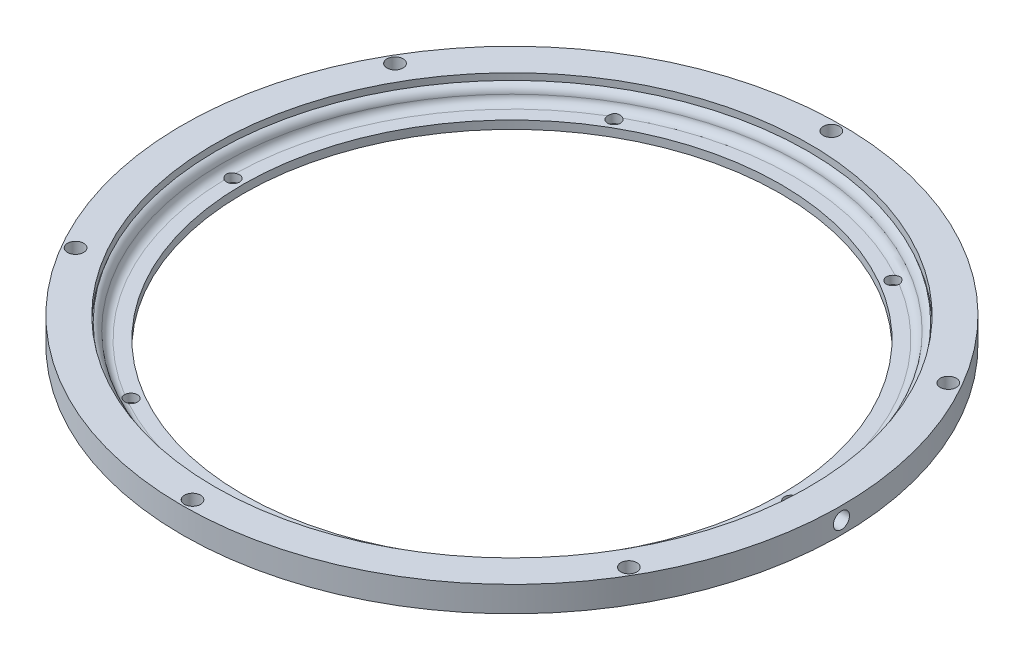
SolidWorks part; units mm, degrees
note: '?' marks a value the reader was unsure of.
ref_plane "Front" through (0, 0, 0) normal (0, 0, 1) x (1, 0, 0)
ref_plane "Top" through (0, 0, 0) normal (0, 1, 0) x (1, 0, 0)
ref_plane "Right" through (0, 0, 0) normal (1, 0, 0) x (0, 0, -1)
ref_axis "Axis1" through (0, 15.0019, 0) along (0, -1, 0)?
sketch "Sketch1" plane through (0, 0, 0) normal (0, 0, 1) x (1, 0, 0)
  line L0 (0, 8.551) -> (0, -4.9357) construction
  line L1 (162.5, 14.2875) -> (162.5, 1.7335)
  line L2 (162.5, 14.2875) -> (146.5, 14.2875)
  line L3 (146.5, 14.2875) -> (146.5, 10.0753)
  line L4 (149.5, 1.7335) -> (162.5, 1.7335)
  line L5 (132.516, 0) -> (148, 0)
  line L6 (132.516, 0) -> (162.5, 14.2875) construction
  line L7 (149.5, 1.7335) -> (149.5, 4.7685)
  line L9 (132.516, 4) -> (132.516, 0)
  line L10 (146.5, 10.0753) -> (149.5, 4.7685) construction
  line L11 (148, 0) -> (148, 4.083)
  line L12 (146, 11.3836) -> (146, 9.8522)
  line L13 (139.0875, 4) -> (132.516, 4)
  arc A0 (146, 9.8522) -> (148, 4.083) centre (147.508, 7.1438) ccw
  arc A1 (146, 11.3836) -> (143.029, 7.5779) centre (147.508, 7.1438) ccw
  arc A2 (139.0875, 4) -> (143.029, 7.5779) centre (139.0875, 7.96) ccw
  arc A3 (149.5, 4.7685) -> (146.5, 10.0753) centre (147.508, 7.1438) ccw
  point P17 (148, 7.4219)
  dimension "D8" = 6.2
  dimension "D9" = 9
  dimension "D2" = 14.2875
  dimension "D3" = 29.984
  dimension "D4" = 16
  dimension "D5" = 12.554
  dimension "D6" = 13
  dimension "D7" = 4
  dimension "D10" = 0.5
  dimension "D11" = 325
  dimension "D12" = 278.175
  dimension "D13" = 1.7335
  dimension "D14" = 265.032
revolve "Revolve2" add sketch "Sketch1" angle 360 about L0
sketch "Sketch2" plane through (0, 0, 0) normal (0, -1, 0) x (1, 0, 0)
  line L0 (0, 0) -> (167.0886, 0) construction
  line L1 (0, 0) -> (86.0025, -148.9607) construction
  line L2 (132.516, 4.1036) -> (132.516, -4.7686) construction
  line L3 (134.516, 3.5121) -> (134.516, -5.9515) construction
  line L4 (137.5, 0) -> (140.484, 0) construction
  line L5 (134.516, 0) -> (137.5, 0) construction
  line L6 (139.657, -6.35) -> (135.2215, -6.35) construction
  line L7 (73.5238, -114.647) -> (75.5358, -118.1318) construction
  arc A0 (75.0109, -111.6598) -> (134.2057, -9.1314) centre (0, 0) ccw
  arc A1 (78.3389, -116.6138) -> (140.1599, -9.5366) centre (0, 0) ccw
  circle A2 centre (0, 0) radius 137.5 construction
  circle A3 centre (0, 0) radius 132.516 construction
  arc A4 (140.1599, -9.5366) -> (134.2057, -9.1314) centre (137.1828, -9.334) ccw
  arc A5 (75.0109, -111.6598) -> (78.3389, -116.6138) centre (76.6749, -114.1368) ccw
  dimension "D2" = 275
  dimension "D1" = 60
  dimension "D3" = 2
  dimension "D4" = 6.35
  dimension "D5" = 6.35
extrude "Cut-Extrude1" cut sketch "Sketch2" against normal offset from surface (0.3165 mm away) 3.81
pattern_circular "CirPattern1" count 6 over 360 about axis through (0, 0, 0) along (0, 1, 0) of "Cut-Extrude1"
sketch "Sketch3" plane through (0, 1.7335, 0) normal (0, -1, 0) x (1, 0, 0)
  line L0 (0, 0) -> (149.5, 86.3139) construction
  line L1 (0, 0) -> (154.2972, -89.0835) construction
  line L2 (0, 0) -> (63.0511, 0) construction
  line L3 (142.7957, 73.2777) -> (134.9914, 68.7719)
  line L4 (134.9914, -68.7719) -> (142.7957, -73.2777)
  line L5 (162.5, 4.9183) -> (162.5, -33.5059) construction
  line L6 (160.5, 8.5668) -> (160.5, -35.0892) construction
  line L7 (151.5, 7.4564) -> (151.5, -22.8744) construction
  line L8 (149.5, -1.1233) -> (149.5, -18.1031) construction
  arc A0 (142.7957, -73.2777) -> (142.7957, 73.2777) centre (0, 0) ccw
  arc A1 (134.9914, -68.7719) -> (134.9914, 68.7719) centre (0, 0) ccw
  circle A2 centre (0, 0) radius 149.5 construction
  circle A3 centre (0, 0) radius 162.5 construction
  dimension "D1" = 60
  dimension "D2" = 30
  dimension "D3" = 7.9375
  dimension "D4" = 7.9375
  dimension "D5" = 2
  dimension "D6" = 2
extrude "Cut-Extrude2" cut sketch "Sketch3" against normal blind 10
pattern_circular "CirPattern2" count 6 over 360 about axis through (0, 0, 0) along (0, 1, 0) of "Cut-Extrude2"
sketch "Sketch5" plane through (0, 4, 0) normal (0, 1, 0) x (-1, 0, 0)
  line L0 (0, 0) -> (-68.75, -119.0785) construction
  line L1 (17.7406, -10.2426) -> (-18.7249, 10.8108) construction
  line L2 (0, 0) -> (0, -87.4239) construction
  circle A0 centre (-68.75, -119.0785) radius 3.175
  dimension "D1" = 6.35
  dimension "D2" = 275
  dimension "D3" = 30
extrude "Cut-Extrude3" cut sketch "Sketch5" against normal through all and the other way through all
pattern_circular "CirPattern3" count 6 over 360 about axis through (0, 0, 0) along (0, 1, 0) of "Cut-Extrude3"
sketch "Sketch8" plane through (0, 0, 0) normal (0, 0, 1) x (1, 0, 0)
  line L1 (151.5, 11.7335) -> (160.5, 11.7335)
  line L2 (151.5, 11.7335) -> (151.5, 1.7335)
  line L3 (151.5, 1.7335) -> (160.5, 1.7335)
  line L4 (160.5, 11.7335) -> (160.5, 1.7335)
  line L5 (142.7957, 1.7335) -> (160.5, 1.7335) construction
  line L6 (142.7957, 11.7335) -> (160.5, 11.7335) construction
  line L7 (151.5, 1.7335) -> (151.5, 11.7335) construction
  line L8 (160.5, 1.7335) -> (160.5, 11.7335) construction
  line L9 (0, 29.5183) -> (0, -14.1535) construction
revolve "Revolve3" add sketch "Sketch8" angle 5 mid plane about L9
sketch "Sketch7" plane through (0, 0, 0) normal (0, 0, 1) x (1, 0, 0)
  line L0 (162.5, 8.0105) -> (169.66, 8.0105) construction
  line L1 (162.5, 1.7335) -> (162.5, 14.2875) construction
  line L2 (148, 0) -> (148, 4.083) construction
  line L3 (162.5, 8.0105) -> (148, 8.0105)
  line L4 (162.5, 8.0105) -> (162.5, 11.9792)
  line L5 (162.5, 11.9792) -> (148, 11.9792)
  line L6 (148, 8.0105) -> (148, 11.9792)
  dimension "D1" = 7.9375
revolve "Cut-Revolve3" cut sketch "Sketch7" angle 360 about L0
sketch "Sketch9" plane through (0, 14.2875, 0) normal (0, 1, 0) x (-1, 0, 0)
  line L0 (0, 0) -> (-153.3926, -88.5612) construction
  line L1 (0, 0) -> (-88.4835, 0) construction
  circle A0 centre (-136.399, -78.75) radius 3.9687
  circle A1 centre (0, 0) radius 157.5 construction
  dimension "D2" = 315
  dimension "D3" = 7.9375
  dimension "D1" = 30
extrude "Cut-Extrude4" cut sketch "Sketch9" against normal through all
pattern_circular "CirPattern4" count 6 over 360 about axis through (0, 0, 0) along (0, 1, 0) of "Cut-Extrude4"
sketch "Sketch10" plane through (0, 0, 0) normal (0, 0, 1) x (1, 0, 0)
  line L0 (168.7798, 8.0105) -> (150.847, 8.0105) construction
  line L1 (162.5, 8.0105) -> (169.66, 8.0105) construction
  line L2 (168.85, 11.0105) -> (168.85, 11.9792)
  line L3 (168.85, 11.9792) -> (181.55, 11.9792) construction
  line L4 (181.55, 11.9792) -> (181.55, 8.0105)
  line L5 (181.55, 8.0105) -> (171.85, 8.0105)
  line L6 (168.85, 11.9792) -> (169.5556, 10.7572)
  line L7 (169.5556, 10.7572) -> (170.2611, 11.9792)
  line L8 (170.2611, 11.9792) -> (170.9667, 10.7572)
  line L9 (170.9667, 10.7572) -> (171.6722, 11.9792)
  line L10 (168.4966, 10.7572) -> (178.8498, 10.7572) construction
  line L11 (169.5556, 10.7572) -> (169.5556, 9.7676) construction
  line L12 (162.5, 11.9792) -> (162.5, 14.2875) construction
  line L13 (171.6722, 11.9792) -> (172.3778, 10.7572)
  line L14 (172.3778, 10.7572) -> (173.0833, 11.9792)
  line L15 (173.0833, 11.9792) -> (173.7889, 10.7572)
  line L16 (173.7889, 10.7572) -> (174.4944, 11.9792)
  line L17 (174.4944, 11.9792) -> (175.2, 10.7572)
  line L18 (175.2, 10.7572) -> (175.9056, 11.9792)
  line L19 (175.9056, 11.9792) -> (176.6111, 10.7572)
  line L20 (176.6111, 10.7572) -> (177.3167, 11.9792)
  line L21 (177.3167, 11.9792) -> (178.0222, 10.7572)
  line L22 (178.0222, 10.7572) -> (178.7278, 11.9792)
  line L23 (178.7278, 11.9792) -> (179.4333, 10.7572)
  line L24 (179.4333, 10.7572) -> (180.1389, 11.9792)
  line L25 (180.1389, 11.9792) -> (181.55, 11.9792)
  line L26 (168.85, 11.0105) -> (171.85, 8.0105)
  dimension "D1" = 12.7
  dimension "D2" = 60
  dimension "D3" = 1.4111
  dimension "D4" = 7.9375
  dimension "D5" = 6.35
  dimension "D6" = 135
  dimension "D7" = 6
revolve "Revolve4" [suppressed] add sketch "Sketch10" angle 360 about L0
sketch "Sketch11" [suppressed] plane through (181.55, 0, 0) normal (1, 0, 0) x (0, 0, -1)
  line L1 (1.3748, 9.3376) -> (-1.3748, 9.3376)
  line L2 (-1.3748, 9.3376) -> (-2.7496, 6.9564)
  line L3 (-2.7496, 6.9564) -> (-1.3748, 4.5751)
  line L4 (-1.3748, 4.5751) -> (1.3748, 4.5751)
  line L5 (1.3748, 4.5751) -> (2.7496, 6.9564)
  line L6 (2.7496, 6.9564) -> (1.3748, 9.3376)
  circle A0 centre (0, 6.9564) radius 2.3813 construction
  circle A1 centre (0, 6.9564) radius 3.9687 construction
  dimension "D1" = 4.7625
extrude "Cut-Extrude5" [suppressed] cut sketch "Sketch11" against normal blind 5.08
